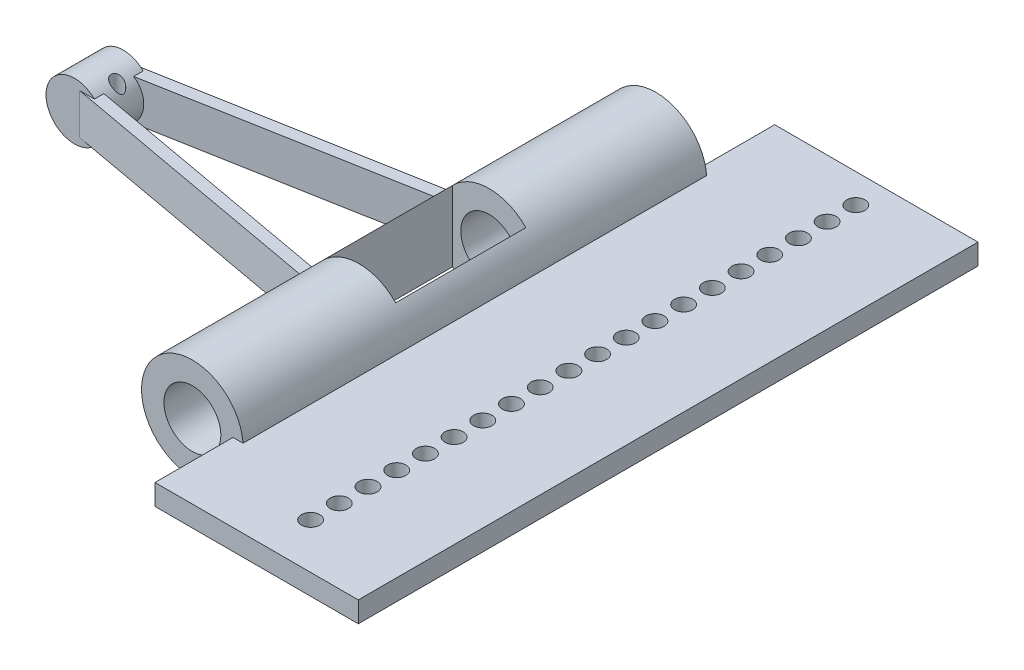
SolidWorks part; units mm, degrees
material "Gray Cast Iron"
ref_plane "Front Plane" through (0, 0, 0) normal (0, 0, 1) x (1, 0, 0)
ref_plane "Top Plane" through (0, 0, 0) normal (0, 1, 0) x (1, 0, 0)
ref_plane "Right Plane" through (0, 0, 0) normal (1, 0, 0) x (0, 0, -1)
sketch "Sketch1" plane through (0, 0, 0) normal (0, 0, 1) x (1, 0, 0)
  circle A0 centre (0, 7) radius 12.5
  dimension "D2" = 25
  dimension "D1" = 7
extrude "Boss-Extrude1" add sketch "Sketch1" along normal mid plane 114
sketch "Sketch2" plane through (0, 0, 0) normal (0, 0, 1) x (1, 0, 0)
  circle A0 centre (0, 7) radius 7
  dimension "D2" = 14
  dimension "D1" = 7
extrude "Cut-Extrude1" cut sketch "Sketch2" against normal mid plane 120
sketch "Sketch3" plane through (0, 0, 0) normal (0, 1, 0) x (1, 0, 0)
  line L0 (-9, -16) -> (9, -16)
  line L1 (9, -16) -> (9, 16)
  line L2 (9, 16) -> (-9, 16)
  line L3 (-9, 16) -> (-9, -16)
  dimension "D1" = 18
  dimension "D2" = 32
  dimension "D3" = 9
  dimension "D4" = 16
extrude "Cut-Extrude2" cut sketch "Sketch3" against normal mid plane 60
sketch "Sketch4" plane through (0, 0, 0) normal (0, 1, 0) x (1, 0, 0)
  line L0 (10, -76.2) -> (60, -76.2)
  line L1 (60, -76.2) -> (60, 76.2)
  line L2 (60, 76.2) -> (10, 76.2)
  line L3 (10, 76.2) -> (10, -76.2)
  circle A0 centre (37.1, 69.05) radius 2.25
  circle A1 centre (37.1, 61.9935) radius 2.25
  circle A2 centre (37.1, 54.937) radius 2.25
  circle A3 centre (37.1, 47.8805) radius 2.25
  circle A4 centre (37.1, 40.824) radius 2.25
  circle A5 centre (37.1, 33.7675) radius 2.25
  circle A6 centre (37.1, 26.711) radius 2.25
  circle A7 centre (37.1, 19.6545) radius 2.25
  circle A8 centre (37.1, 12.598) radius 2.25
  circle A9 centre (37.1, 5.5415) radius 2.25
  circle A10 centre (37.1, -1.515) radius 2.25
  circle A11 centre (37.1, -8.5715) radius 2.25
  circle A12 centre (37.1, -15.628) radius 2.25
  circle A13 centre (37.1, -22.6845) radius 2.25
  circle A14 centre (37.1, -29.741) radius 2.25
  circle A15 centre (37.1, -36.7975) radius 2.25
  circle A16 centre (37.1, -43.854) radius 2.25
  circle A17 centre (37.1, -50.9105) radius 2.25
  circle A18 centre (37.1, -57.967) radius 2.25
  circle A19 centre (37.1, -65.0235) radius 2.25
  dimension "D3" = 4.5
  dimension "D6" = 4.5
  dimension "D9" = 4.5
  dimension "D12" = 4.5
  dimension "D15" = 4.5
  dimension "D18" = 4.5
  dimension "D21" = 4.5
  dimension "D24" = 4.5
  dimension "D27" = 4.5
  dimension "D30" = 4.5
  dimension "D33" = 4.5
  dimension "D36" = 4.5
  dimension "D39" = 4.5
  dimension "D42" = 4.5
  dimension "D45" = 4.5
  dimension "D48" = 4.5
  dimension "D51" = 4.5
  dimension "D54" = 4.5
  dimension "D57" = 4.5
  dimension "D60" = 4.5
  dimension "D1" = 37.1
  dimension "D2" = 69.05
  dimension "D4" = 37.1
  dimension "D5" = 61.9935
  dimension "D7" = 37.1
  dimension "D8" = 54.937
  dimension "D10" = 37.1
  dimension "D11" = 47.8805
  dimension "D13" = 37.1
  dimension "D14" = 40.824
  dimension "D16" = 37.1
  dimension "D17" = 33.7675
  dimension "D19" = 37.1
  dimension "D20" = 26.711
  dimension "D22" = 37.1
  dimension "D23" = 19.6545
  dimension "D25" = 37.1
  dimension "D26" = 12.598
  dimension "D28" = 37.1
  dimension "D29" = 5.5415
  dimension "D31" = 37.1
  dimension "D32" = 1.515
  dimension "D34" = 37.1
  dimension "D35" = 8.5715
  dimension "D37" = 37.1
  dimension "D38" = 15.628
  dimension "D40" = 37.1
  dimension "D41" = 22.6845
  dimension "D43" = 37.1
  dimension "D44" = 29.741
  dimension "D46" = 37.1
  dimension "D47" = 36.7975
  dimension "D49" = 37.1
  dimension "D50" = 43.854
  dimension "D52" = 37.1
  dimension "D53" = 50.9105
  dimension "D55" = 37.1
  dimension "D56" = 57.967
  dimension "D58" = 37.1
  dimension "D59" = 65.0235
  dimension "D61" = 50
  dimension "D62" = 152.4
  dimension "D63" = 10
  dimension "D64" = 76.2
extrude "Boss-Extrude2" add sketch "Sketch4" along normal blind 5.1 from offset 2.9
sketch "Sketch5" plane through (0, 0, 0) normal (0, 1, 0) x (1, 0, 0)
  line L0 (-9, 15.68) -> (-9, 18.68)
  line L1 (-9, 18.68) -> (-80, 5.77)
  line L2 (-80, 5.77) -> (-80, 2.77)
  line L3 (-80, 2.77) -> (-9, 15.68)
  line L4 (-9, -15.68) -> (-9, -18.68)
  line L5 (-9, -18.68) -> (-80, -5.77)
  line L6 (-80, -5.77) -> (-80, -2.77)
  line L7 (-80, -2.77) -> (-9, -15.68)
  dimension "D1" = 9
  dimension "D2" = 15.68
  dimension "D3" = 3
  dimension "D4" = 71
  dimension "D5" = 12.91
  dimension "D6" = 3
  dimension "D7" = 9
  dimension "D8" = 15.68
  dimension "D9" = 3
  dimension "D10" = 71
  dimension "D11" = 12.91
  dimension "D12" = 3
extrude "Boss-Extrude3" add sketch "Sketch5" along normal blind 10 from offset 2
sketch "Sketch6" plane through (0, 0, 0) normal (0, 0, 1) x (1, 0, 0)
  circle A0 centre (-80, 7) radius 7
  dimension "D3" = 14
  dimension "D1" = 80
  dimension "D2" = 7
extrude "Boss-Extrude4" add sketch "Sketch6" along normal mid plane 12
sketch "Sketch7" plane through (0, 0, 0) normal (0, 1, 0) x (1, 0, 0)
  circle A0 centre (-75.5, 0) radius 1.5
  dimension "D2" = 3
  dimension "D1" = 75.5
extrude "Cut-Extrude3" cut sketch "Sketch7" against normal mid plane 28
